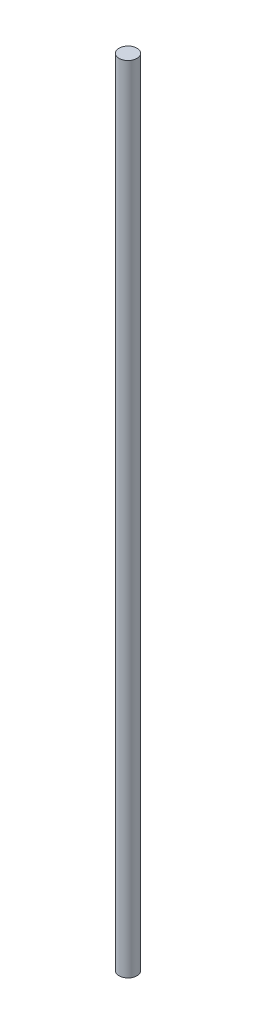
SolidWorks part; units mm, degrees
ref_plane "Front Plane" through (0, 0, 0) normal (0, 0, 1) x (1, 0, 0)
ref_plane "Top Plane" through (0, 0, 0) normal (0, 1, 0) x (1, 0, 0)
ref_plane "Right Plane" through (0, 0, 0) normal (1, 0, 0) x (0, 0, -1)
sketch "Sketch1" plane through (0, 0, 0) normal (0, 1, 0) x (1, 0, 0)
  circle A0 centre (0, 0) radius 5
  dimension "D1" = 10
extrude "Boss-Extrude2" add sketch "Sketch1" along normal blind 446
